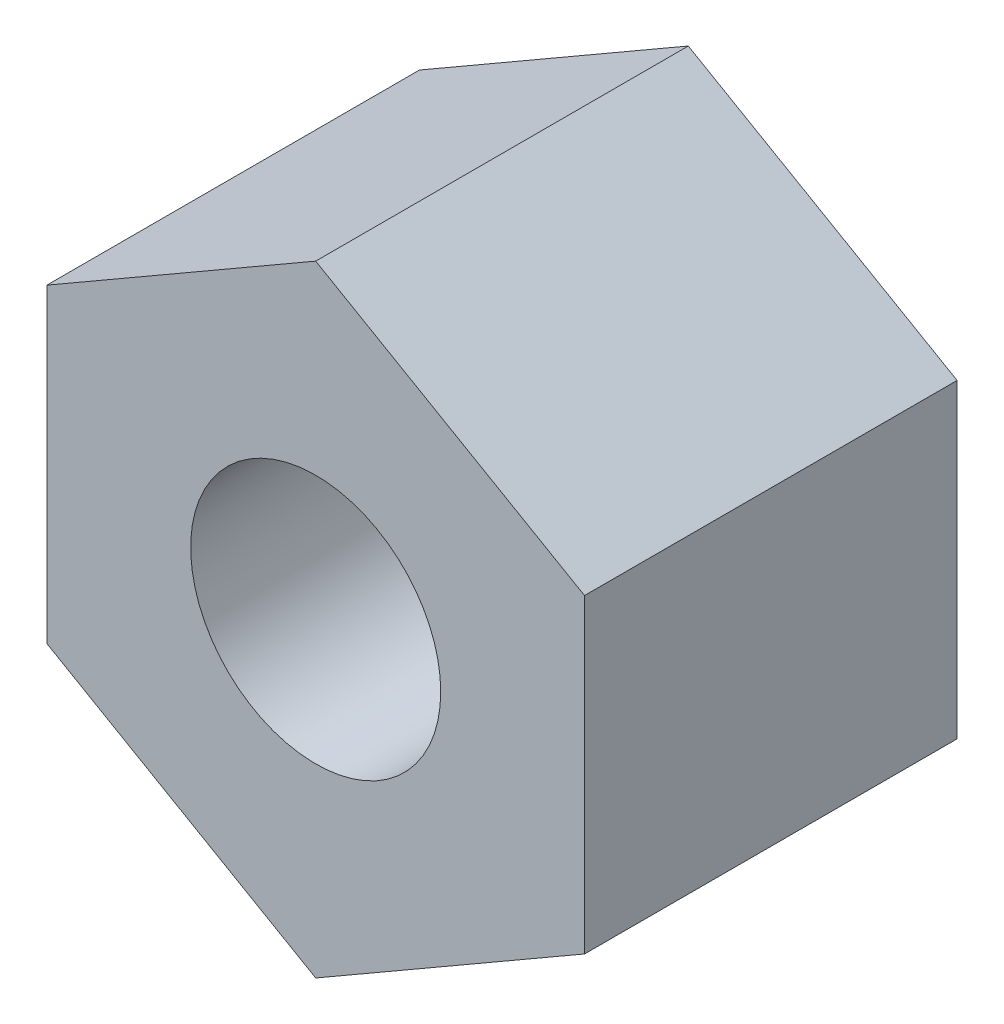
SolidWorks part; units mm, degrees
ref_plane "Front Plane" through (0, 0, 0) normal (1, 0, 0) x (0, 1, 0)
ref_plane "Top Plane" through (0, 0, 0) normal (0, 0, 1) x (0, 1, 0)
ref_plane "Right Plane" through (0, 0, 0) normal (0, 1, 0) x (-1, 0, 0)
sketch "Sketch1" plane through (0, 0, 0) normal (0, 0, 1) x (0, 1, 0)
  line L1 (4.9652, 0) -> (2.4826, 4.3)
  line L2 (2.4826, 4.3) -> (-2.4826, 4.3)
  line L3 (-2.4826, 4.3) -> (-4.9652, 0)
  line L4 (-4.9652, 0) -> (-2.4826, -4.3)
  line L5 (-2.4826, -4.3) -> (2.4826, -4.3)
  line L6 (2.4826, -4.3) -> (4.9652, 0)
  circle A0 centre (0, 0) radius 4.3 construction
  dimension "D1" = 8.6
extrude "Boss-Extrude1" add sketch "Sketch1" along normal blind 5.96
sketch "Sketch2" plane through (0, 0, 0) normal (0, 0, 1) x (0, 1, 0)
  circle A0 centre (0, 0) radius 2
  dimension "D1" = 4
extrude "Cut-Extrude1" cut sketch "Sketch2" along normal up to next
